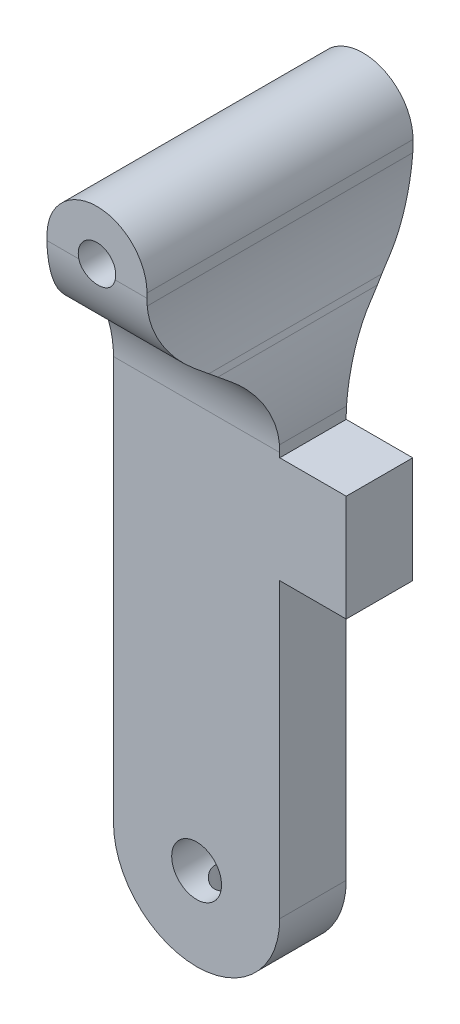
SolidWorks part; units mm, degrees
note: '?' marks a value the reader was unsure of.
ref_plane "Front Plane" through (0, 0, 0) normal (0, 0, 1) x (1, 0, 0)
ref_plane "Top Plane" through (0, 0, 0) normal (0, 1, 0) x (1, 0, 0)
ref_plane "Right Plane" through (0, 0, 0) normal (1, 0, 0) x (0, 0, -1)
sketch "Sketch1" plane through (0, 0, 0) normal (0, 0, 1) x (1, 0, 0)
  line L1 (-28.2601, 37.8507) -> (-6.0351, 37.8507)
  line L2 (-28.2601, 37.8507) -> (-28.2601, -29.7895)
  line L3 (-28.2601, -29.7895) -> (-6.0351, -29.7895)
  line L4 (-6.0351, 37.8507) -> (-6.0351, -29.7895)
  dimension "D1" = 22.225
  dimension "D2" = 67.6402
extrude "Boss-Extrude1" add sketch "Sketch1" along normal blind 25.4
sketch "Sketch2" plane through (0, 0, 25.4) normal (0, 0, 1) x (1, 0, 0)
  line L0 (-6.0351, 37.8507) -> (-28.2601, 37.8507) construction
  line L1 (-6.0351, -29.7895) -> (-6.0351, 37.8507) construction
  line L2 (-15.5347, 33.0755) -> (-15.5347, 31.9888)
  line L3 (-28.2601, -29.7895) -> (-6.0351, -29.7895) construction
  line L4 (-28.2601, 37.8507) -> (-28.2601, -29.7895) construction
  line L5 (-12.3851, 16.2607) -> (-12.3851, 17.3474)
  line L6 (-6.0351, -29.7895) -> (-12.3851, -29.7895)
  line L7 (-6.0351, -29.7895) -> (-6.0351, 6.1007)
  line L8 (-6.0351, 6.1007) -> (-12.3851, 6.1007)
  line L9 (-12.3851, -29.7895) -> (-12.3851, 6.1007)
  line L10 (-6.0351, 16.2607) -> (-12.3851, 16.2607)
  line L11 (-26.5732, 24.8955) -> (-26.772, 24.4407)
  line L12 (-12.3851, 16.2607) -> (-28.2601, 16.2607) construction
  line L13 (-28.2601, 16.2607) -> (-28.2601, 17.3201)
  line L14 (-25.0851, 33.0755) -> (-25.0851, 32.0161)
  line L15 (-6.0351, 16.2607) -> (-6.0351, 37.8507)
  line L16 (-13.8524, 24.4201) -> (-14.0675, 24.9162)
  circle A0 centre (-20.3099, 33.0755) radius 1.7907
  circle A3 centre (-20.3099, 33.0755) radius 4.7752
  circle A4 centre (-20.3226, -21.852) radius 7.9375
  arc A5 (-28.2601, 17.3201) -> (-26.772, 24.4407) centre (-10.4801, 17.3201) cw
  arc A6 (-25.0851, 32.0161) -> (-26.5732, 24.8955) centre (-42.8651, 32.0161) cw
  arc A7 (-15.5347, 31.9888) -> (-14.0675, 24.9162) centre (2.2453, 31.9888) ccw
  arc A8 (-12.3851, 17.3474) -> (-13.8524, 24.4201) centre (-30.1651, 17.3474) ccw
  point P29 (-28.2601, 21.0359)
  dimension "D1" = 4.7752
  dimension "D7" = 35.8902
  dimension "D10" = 15.875
  dimension "D11" = 9.5504
  dimension "D6" = 17.78
  dimension "D2" = 7.9502
  dimension "D8" = 21.59
extrude "Cut-Extrude2" cut sketch "Sketch2" against normal blind 25.4
sketch "Sketch4" plane through (-6.0351, 0, 0) normal (1, 0, 0) x (0, 0, -1)
  line L0 (0, 6.1007) -> (0, 16.2607) construction
  line L2 (-9.525, -29.7941) -> (0, -29.7941)
  line L3 (0, -29.7941) -> (0, 32.6378)
  line L12 (-25.4, 6.1007) -> (0, 6.1007) construction
  line L15 (-15.875, -29.8159) -> (-25.4, -29.8159)
  line L16 (-25.4, -29.8159) -> (-25.4, 32.6378)
  line L20 (-15.875, 16.2607) -> (-15.875, 16.6985)
  line L22 (-25.4, 6.1007) -> (0, 6.1007)
  line L27 (-15.875, -29.8159) -> (-15.875, 16.2607)
  line L28 (-9.525, -29.7941) -> (-9.525, 16.2607)
  line L31 (-9.525, 16.2607) -> (-9.525, 16.6985)
  line L34 (-19.3239, 23.6663) -> (-21.9511, 25.67)
  line L35 (-6.0761, 23.6663) -> (-3.4489, 25.67)
  arc A0 (-9.525, 16.6985) -> (-6.0761, 23.6663) centre (-0.762, 16.6985) cw
  arc A1 (-15.875, 16.6985) -> (-19.3239, 23.6663) centre (-24.638, 16.6985) ccw
  arc A2 (0, 32.6378) -> (-3.4489, 25.67) centre (-8.763, 32.6378) cw
  arc A3 (-25.4, 32.6378) -> (-21.9511, 25.67) centre (-16.637, 32.6378) ccw
  line M1 (-25.4, 16.2607) -> (-25.4, 6.1007)
  line M2 (-25.4, 6.1007) -> (0, 6.1007)
  line M3 (0, 6.1007) -> (0, 16.2607)
  line M4 (0, 16.2607) -> (-25.4, 16.2607)
  dimension "D3" = 8.763
  dimension "D1" = 6.35
  dimension "D2" = 9.525
extrude "Cut-Extrude3" cut sketch "Sketch4" against normal through all contours L3 A2 L35 A0 L31 M4 | L28 M2 M3 M4 | L28 L2 L3 M2 | L15 L27 L16 M2 | L27 M2 M4 M1 | A3 L16 L20 A1 L34 M4
ref_point "Point1"
ref_point "Point2"
ref_point "Point3"
ref_plane "Plane1" through (0, 0, 12.7) normal (0, 0, 1) x (1, 0, 0)
sketch "Sketch5" plane through (0, 0, 9.525) normal (0, 0, -1) x (-1, 0, 0)
  circle A0 centre (20.3226, -21.852) radius 2.3812 construction
  circle A1 centre (20.3226, -21.852) radius 2.3813
extrude "Cut-Extrude4" cut sketch "Sketch5" against normal up to surface (6.35 mm away) up to face at (-14.7664, 3.3098, 15.875)
ref_axis "Axis1" through (-20.3226, -21.852, 15.875) along (0, 0, -1)?
ref_point "Point4"
ref_plane "Plane2" through (0, -29.7895, 0) normal (0, -1, 0) x (-1, 0, 0)
ref_point "Point5"
sketch "Sketch6" plane through (0, -29.7895, 0) normal (0, -1, 0) x (1, 0, 0)
  circle A0 centre (-20.3226, 12.7) radius 1.4555
extrude "Cut-Extrude5" cut sketch "Sketch6" against normal up to vertex contours A0
